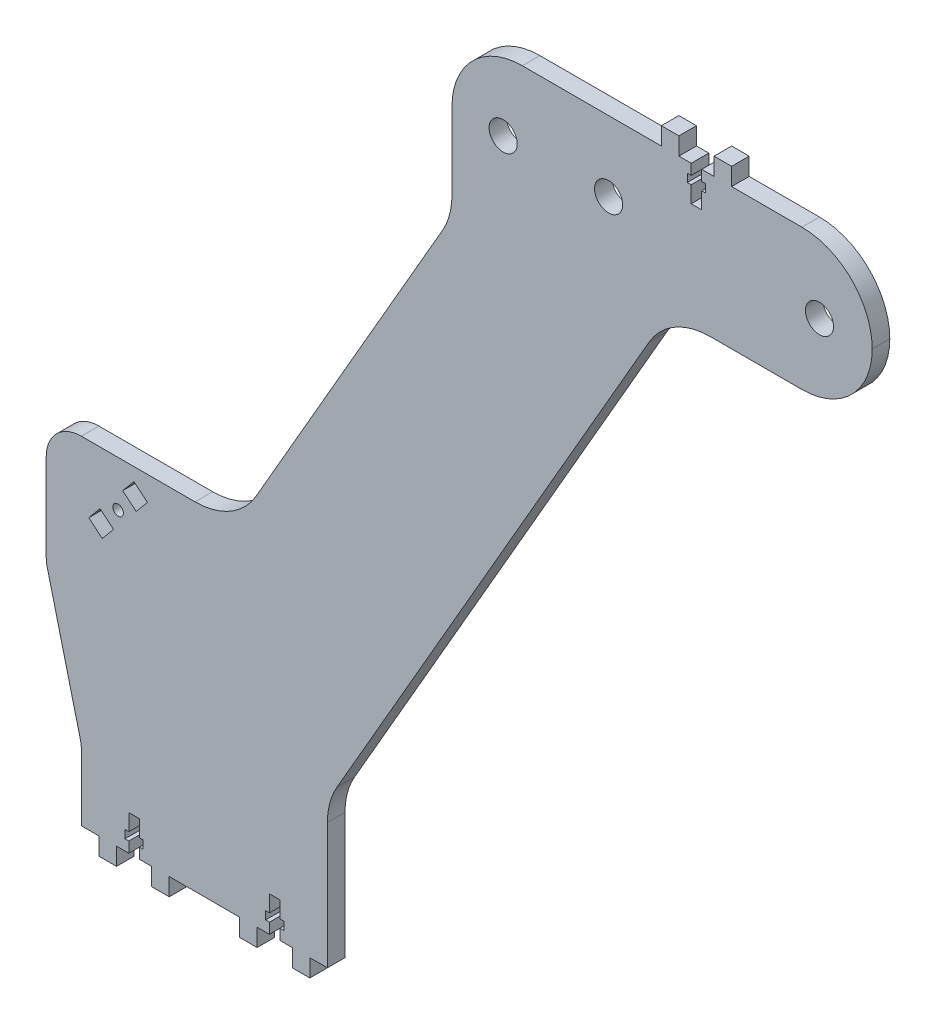
SolidWorks part; units mm, degrees
ref_plane "Plan de face" through (0, 0, 0) normal (0, 0, 1) x (1, 0, 0)
ref_plane "Plan de dessus" through (0, 0, 0) normal (0, 1, 0) x (1, 0, 0)
ref_plane "Plan de droite" through (0, 0, 0) normal (1, 0, 0) x (0, 0, -1)
sketch "Esquisse1" plane through (0, 0, 0) normal (0, 0, 1) x (1, 0, 0)
  line L0 (0, 0) -> (0, 38.8315) construction
  line L1 (-33.9845, 0) -> (30.6321, 0) construction
  line L2 (-20, 0) -> (-20, 33.6786) construction
  line L3 (-21.5, 0) -> (-25, 0)
  line L4 (-25, -5) -> (-30, -5)
  line L5 (-30, -5) -> (-30, 0)
  line L6 (-25, -5) -> (-25, 0)
  line L7 (-18.5, 0) -> (-15, 0)
  line L8 (-15, 0) -> (-15, -5)
  line L9 (-15, -5) -> (-10, -5)
  line L10 (-10, -5) -> (-10, 0)
  line L11 (-21.5, 0) -> (-18.5, 0) construction
  line L12 (-18.5, 0) -> (-18.5, 3)
  line L13 (-18.5, 5.3) -> (-17.4, 5.3)
  line L14 (-22.6, 3) -> (-22.6, 5.3)
  line L15 (-17.4, 3) -> (-18.5, 3)
  line L16 (-18.5, 5.3) -> (-18.5, 10)
  line L17 (-18.5, 10) -> (-21.5, 10)
  line L18 (-21.5, 10) -> (-21.5, 5.3)
  line L19 (-21.5, 3) -> (-22.6, 3)
  line L20 (-17.4, 5.3) -> (-17.4, 3)
  line L21 (-22.6, 5.3) -> (-21.5, 5.3)
  line L22 (-21.5, 3) -> (-21.5, 0)
  line L23 (-20, 10) -> (-20, 0) construction
  line L24 (10, -5) -> (10, 0)
  line L25 (15, -5) -> (10, -5)
  line L26 (15, 0) -> (15, -5)
  line L27 (18.5, 0) -> (15, 0)
  line L28 (18.5, 0) -> (18.5, 3)
  line L29 (17.4, 3) -> (18.5, 3)
  line L30 (17.4, 5.3) -> (17.4, 3)
  line L31 (18.5, 5.3) -> (17.4, 5.3)
  line L32 (18.5, 5.3) -> (18.5, 10)
  line L33 (18.5, 10) -> (21.5, 10)
  line L34 (21.5, 10) -> (21.5, 5.3)
  line L35 (22.6, 5.3) -> (21.5, 5.3)
  line L36 (22.6, 3) -> (22.6, 5.3)
  line L37 (21.5, 3) -> (22.6, 3)
  line L38 (21.5, 3) -> (21.5, 0)
  line L39 (21.5, 0) -> (25, 0)
  line L40 (25, -5) -> (25, 0)
  line L41 (25, -5) -> (30, -5)
  line L42 (30, -5) -> (30, 0)
  line L43 (-10, 0) -> (10, 0)
  line L44 (30, 0) -> (35, 0)
  line L45 (35, 0) -> (35, 95.9934) construction
  line L46 (35, 95.9934) -> (-35, 95.9934) construction
  line L47 (-35, 95.9934) -> (-35, 0) construction
  line L48 (-35, 0) -> (-30, 0)
  line L52 (0, 20) -> (-35, 20) construction
  line L54 (-10, 95.9934) -> (-35, 95.9934)
  line L55 (-35, 20) -> (-57.9813, 39.2836) construction
  line L56 (-57.9813, 39.2836) -> (9.2875, 119.4515) construction
  line L57 (-35, 20) -> (-54.2836, 42.9813) construction
  line L58 (-54.2836, 42.9813) -> (25.8842, 110.2501) construction
  line L59 (-35, 20) -> (-50, 45.9808) construction
  line L60 (-50, 45.9808) -> (40.631, 98.3066) construction
  line L61 (-35, 20) -> (-45.2606, 48.1908) construction
  line L62 (-45.2606, 48.1908) -> (53.0798, 83.9838) construction
  line L63 (-22.5, 95.9934) -> (-22.5, 106.8704) construction
  line L64 (-35, 95.9934) -> (-45, 95.9934)
  line L65 (-45, 95.9934) -> (-45, 60)
  line L66 (-45, 60) -> (-35, 20)
  line L67 (-35, 20) -> (-35, 0)
  line L68 (97.6728, 250) -> (8.8937, 95.9934) construction
  line L69 (132.3272, 210) -> (35, 41.165)
  line L70 (35, 41.165) -> (35, 0)
  line L71 (97.6728, 250) -> (132.3272, 210) construction
  line L72 (97.6728, 250) -> (190, 250) construction
  line L73 (190, 250) -> (190, 210)
  line L74 (190, 210) -> (132.3272, 210)
  line L75 (115, 230) -> (190, 230) construction
  line L76 (8.8937, 95.9934) -> (-10, 95.9934)
  line L77 (8.8937, 95.9934) -> (70.4429, 202.7638)
  line L79 (70.4429, 202.7638) -> (70.4429, 250)
  line L80 (70.4429, 250) -> (97.6728, 250)
  line L81 (115, 230) -> (85, 230) construction
  line L82 (150, 250) -> (190, 250)
  line L83 (130, 250) -> (97.6728, 250)
  line L84 (140, 250) -> (140, 238.7792) construction
  line L85 (141.5, 250) -> (145, 250)
  line L86 (145, 255) -> (150, 255)
  line L87 (150, 255) -> (150, 250)
  line L88 (145, 255) -> (145, 250)
  line L89 (138.5, 250) -> (135, 250)
  line L90 (135, 250) -> (135, 255)
  line L91 (135, 255) -> (130, 255)
  line L92 (130, 255) -> (130, 250)
  line L93 (141.5, 250) -> (138.5, 250) construction
  line L94 (138.5, 250) -> (138.5, 247)
  line L95 (138.5, 244.7) -> (137.4, 244.7)
  line L96 (142.6, 247) -> (142.6, 244.7)
  line L97 (137.4, 247) -> (138.5, 247)
  line L98 (138.5, 244.7) -> (138.5, 240)
  line L99 (138.5, 240) -> (141.5, 240)
  line L100 (141.5, 240) -> (141.5, 244.7)
  line L101 (141.5, 247) -> (142.6, 247)
  line L102 (137.4, 244.7) -> (137.4, 247)
  line L103 (142.6, 244.7) -> (141.5, 244.7)
  line L104 (141.5, 247) -> (141.5, 250)
  line L105 (140, 240) -> (140, 250) construction
  arc A1 (35, 58.7298) -> (-10, 95.9934) centre (-35, 20) ccw construction
  circle A7 centre (115, 230) radius 4
  circle A8 centre (175, 230) radius 4
  circle A9 centre (85, 230) radius 4
  point P68 (-35, 20)
  point P86 (70.4429, 226.3819)
  point P90 (115, 230)
  point P97 (0, 0)
  line B0 (-29.6722, 80.7998) -> (-32.8861, 76.9696)
  line B1 (-29.6722, 80.7998) -> (-25.842, 77.5859)
  line B2 (-25.842, 77.5859) -> (-29.0559, 73.7556)
  line B3 (-32.8861, 76.9696) -> (-29.0559, 73.7556)
  line B4 (-23.2443, 88.4602) -> (-20.0304, 92.2905)
  line B5 (-23.2443, 88.4602) -> (-19.4141, 85.2463)
  line B6 (-19.4141, 85.2463) -> (-16.2001, 89.0765)
  line B7 (-20.0304, 92.2905) -> (-16.2001, 89.0765)
  line B8 (-24.5431, 83.023) -> (-29.8843, 87.5048) construction
  circle B9 centre (-24.5431, 83.023) radius 1.5
  dimension "D14" = 80
  dimension "D25" = 8
  dimension "D1" = 20
  dimension "D2" = 10
  dimension "D3" = 5
  dimension "D4" = 5
  dimension "D5" = 5.2
  dimension "D6" = 3
  dimension "D7" = 2.3
  dimension "D8" = 3
  dimension "D9" = 10
  dimension "D10" = 5
  dimension "D11" = 5
  dimension "D12" = 10
  dimension "D13" = 20
  dimension "D15" = 25
  dimension "D16" = 30
  dimension "D17" = 50
  dimension "D18" = 55
  dimension "D20" = 10
  dimension "D21" = 40
  dimension "D22" = 230
  dimension "D23" = 80
  dimension "D24" = 50
  dimension "D26" = 60
  dimension "D27" = 15
  dimension "D28" = 40
  dimension "D29" = 30
  dimension "D30" = 15
  dimension "D31" = 25
  dimension "D32" = 10
  dimension "D33" = 5
  dimension "D34" = 5
  dimension "D35" = 5.2
  dimension "D36" = 3
  dimension "D37" = 2.3
  dimension "D38" = 3
  dimension "D39" = 10
  dimension "D19" = 4
sketch_block_instance "Trou M3 plots 5mm-1"
sketch_block "Trou M3 plots 5mm" parameters "D2"=3, "D1"=5, "D3"=5, "D4"=10
sketch_block_instance "Trou M3 plots 5mm-6"
sketch_block_instance "Trou M3 plots 5mm-7"
sketch_block_instance "Trou M3 plots 5mm-8"
extrude "Boss.-Extru.1" add sketch "Esquisse1" along normal blind 5
fillet "Congé1" radius 10 3 edges at (-35, 20, 2.5) (-45, 60, 2.5) (-45, 95.9934, 2.5)
fillet "Congé2" radius 20 7 edges at (35, 41.165, 2.5) (132.3272, 210, 2.5) (190, 210, 2.5) (70.4429, 250, 2.5) (190, 250, 2.5) (8.8937, 95.9934, 2.5) (70.4429, 202.7638, 2.5)
